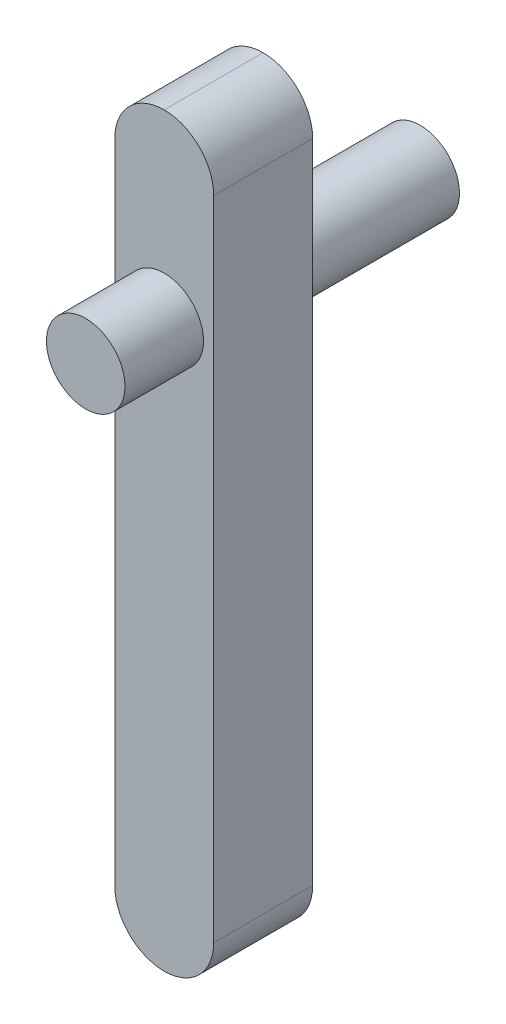
SolidWorks part; units mm, degrees
ref_plane "Front Plane" through (0, 0, 0) normal (0, 0, 1) x (1, 0, 0)
ref_plane "Top Plane" through (0, 0, 0) normal (0, 1, 0) x (1, 0, 0)
ref_plane "Right Plane" through (0, 0, 0) normal (1, 0, 0) x (0, 0, -1)
sketch "Sketch1" plane through (0, 0, 0) normal (0, 0, 1) x (1, 0, 0)
  line L0 (4, 25.4) -> (4, 34.925)
  line L2 (-4, 25.4) -> (-4, -25.4)
  line L3 (-4, -25.4) -> (4, -25.4)
  line L4 (4, 25.4) -> (4, -25.4)
  line L5 (-4, 25.4) -> (4, -25.4) construction
  line L6 (-4, -25.4) -> (4, 25.4) construction
  line L7 (4, 34.925) -> (-4, 34.925)
  line L8 (-4, 34.925) -> (-4, 25.4)
  line L9 (-4, 25.4) -> (4, 25.4) construction
  point P0 (0, 0)
  dimension "D1" = 8
  dimension "D2" = 50.8
  dimension "D3" = 34.925
extrude "Boss-Extrude1" add sketch "Sketch1" along normal blind 8
fillet "Fillet1" radius 4 4 edges at (-4, -25.4, 4) (4, -25.4, 4) (4, 34.925, 4) (-4, 34.925, 4)
sketch "Sketch2" plane through (0, 0, 8) normal (0, 0, 1) x (1, 0, 0)
  circle A0 centre (0, 20.32) radius 3.175
  dimension "D1" = 6.35
  dimension "D2" = 20.32
extrude "Boss-Extrude2" add sketch "Sketch2" along normal blind 6.35 and the other way blind 20.7
